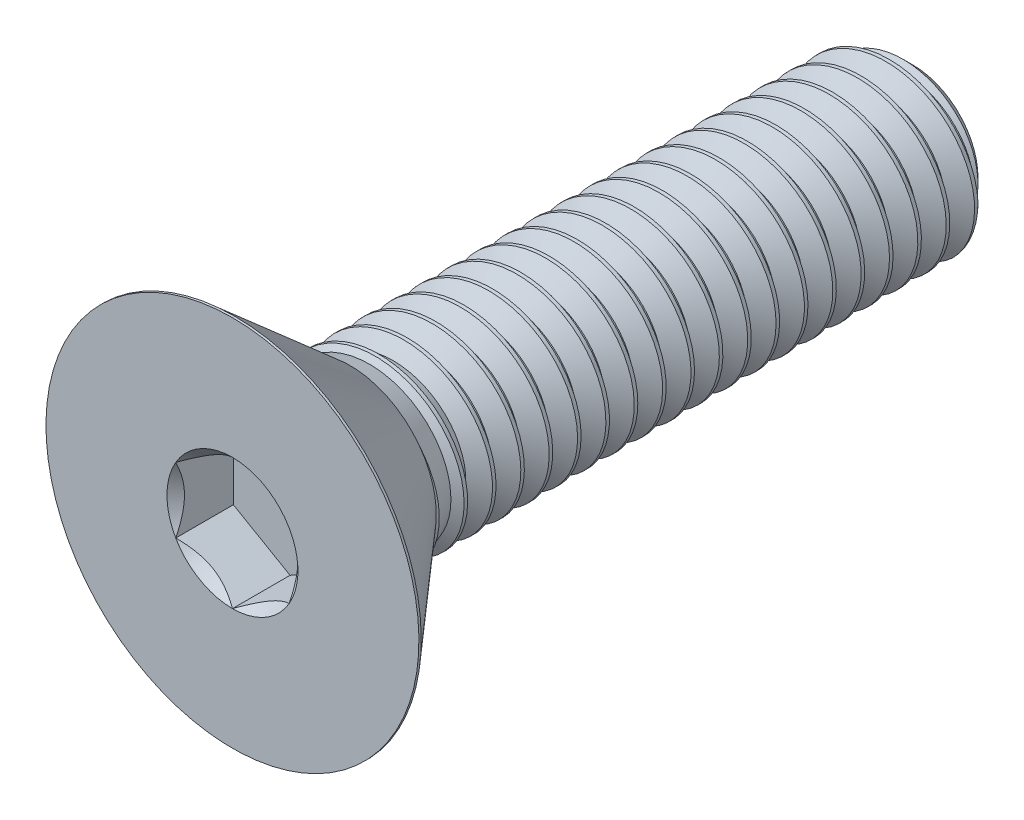
SolidWorks part; units mm, degrees
material "AISI 1020"
ref_plane "Front Plane" through (0, 0, 0) normal (0, 0, 1) x (1, 0, 0)
ref_plane "Top Plane" through (0, 0, 0) normal (0, 1, 0) x (1, 0, 0)
ref_plane "Right Plane" through (0, 0, 0) normal (1, 0, 0) x (0, 0, -1)
sketch "Sketch1" plane through (0, 0, 0) normal (1, 0, 0) x (0, 0, -1)
  line L0 (-9.525, 0) -> (9.525, 0) construction
  line L1 (-9.525, 0) -> (-9.525, 5.2197)
  line L2 (-9.525, 5.2197) -> (-9.4605, 5.2197)
  line L3 (-9.4605, 5.2197) -> (-6.2992, 2.4716)
  line L4 (-9.4605, -5.2197) -> (-6.2992, -2.4716)
  line L5 (9.525, 0) -> (9.525, 2.413)
  line L6 (9.525, 2.413) -> (-6.2992, 2.413)
  line L7 (8.9297, 2.413) -> (9.525, 1.8177)
  line L8 (9.4754, 2.4989) -> (9.8723, 1.8115) construction
  line L9 (9.8723, 1.8115) -> (10.2691, 2.4989) construction
  line L10 (10.2691, 2.4989) -> (9.4754, 2.4989) construction
  line L11 (9.5002, 2.456) -> (10.2443, 2.456)
  line L12 (10.2443, 2.456) -> (9.9219, 1.8974)
  line L13 (9.9219, 1.8974) -> (9.8227, 1.8974)
  line L14 (9.8227, 1.8974) -> (9.5002, 2.456)
  line L15 (9.8723, 1.8974) -> (9.8723, 1.8115) construction
  line L16 (9.525, 2.413) -> (10.2195, 2.413) construction
  line L17 (9.8723, 2.4989) -> (9.8723, 2.413) construction
  line L18 (9.525, -2.413) -> (-6.2992, -2.413)
  arc A0 (-6.2992, 2.4716) -> (-6.1424, 2.413) centre (-6.1424, 2.6521) ccw
  point P2 (0, 0)
  point P23 (-7.9121, 0)
  point P27 (9.8723, 2.456)
  point P30 (8.3344, -2.413)
  point P31 (-6.2992, 5.2197)
  point P33 (-6.2992, -5.2197)
  point P34 (-9.4605, -5.2197)
  dimension "Length" = 19.05
  dimension "Head Height" = 3.2258
  dimension "Head Diameter" = 10.4394
  dimension "Countersink Angle" = 82
  dimension "Screw Size Decimal Equivalent" = 4.826
  dimension "Pitch" = 0.7937
  dimension "D4" = 0.0992
  dimension "D3" = 45
  dimension "D5" = 0.5953
  dimension "D6" = 1.6129
  dimension "D1" = 1.1906
  dimension "D7" = 0.0645
sketch "Sketch8" plane through (0, 0, 0) normal (0, 0, 1) x (1, 0, 0)
  line L1 (0, 1.8331) -> (-1.5875, 0.9165)
  line L2 (-1.5875, 0.9165) -> (-1.5875, -0.9165)
  line L3 (-1.5875, -0.9165) -> (0, -1.8331)
  line L4 (0, -1.8331) -> (1.5875, -0.9165)
  line L5 (1.5875, -0.9165) -> (1.5875, 0.9165)
  line L6 (1.5875, 0.9165) -> (0, 1.8331)
  circle A0 centre (0, 0) radius 1.5875 construction
  dimension "Drive Size" = 3.175
sketch "Sketch2" plane through (0, 0, 0) normal (1, 0, 0) x (0, 0, -1)
  line L0 (-9.4605, 5.2197) -> (-6.2992, 2.4716) construction
  line L1 (-9.525, 0) -> (-9.525, 5.2197) construction
  line L2 (-9.4605, 5.2197) -> (-6.2317, 2.413)
  line L3 (-9.525, 0) -> (-9.525, 5.2197)
  line L4 (-9.525, 5.2197) -> (-9.4605, 5.2197) construction
  line L5 (-9.525, 5.2197) -> (-9.4605, 5.2197)
  line L6 (-6.2317, 2.413) -> (8.9297, 2.413)
  line L7 (8.9297, 2.413) -> (9.525, 1.8177)
  line L8 (9.525, 1.8177) -> (9.525, 0)
  line L9 (9.525, 0) -> (-9.525, 0)
revolve "Revolve1" add sketch "Sketch2" angle 360 about L9
sketch "Sketch9" plane through (0, 0, 9.525) normal (0, 0, 1) x (1, 0, 0)
  line L0 (1.5875, -0.9165) -> (1.5875, 0.9165) construction
  line L1 (0, -1.8331) -> (1.5875, -0.9165) construction
  line L2 (-1.5875, -0.9165) -> (0, -1.8331) construction
  line L3 (-1.5875, 0.9165) -> (-1.5875, -0.9165) construction
  line L4 (0, 1.8331) -> (-1.5875, 0.9165) construction
  line L5 (1.5875, 0.9165) -> (0, 1.8331) construction
  line L6 (1.5875, -0.9165) -> (1.5875, 0.9165)
  line L7 (0, -1.8331) -> (1.5875, -0.9165)
  line L8 (-1.5875, -0.9165) -> (0, -1.8331)
  line L9 (-1.5875, 0.9165) -> (-1.5875, -0.9165)
  line L10 (0, 1.8331) -> (-1.5875, 0.9165)
  line L11 (1.5875, 0.9165) -> (0, 1.8331)
sketch "Sketch10" plane through (0, 0, 9.525) normal (0, 0, 1) x (1, 0, 0)
  circle A0 centre (0, 0) radius 1.8331
extrude "Cut-Extrude2" cut sketch "Sketch10" against normal up to vertex (1.6129 mm away) draft 45 up to point (0, 0, 7.9121)
extrude "Cut-Extrude1" cut sketch "Sketch9" against normal up to vertex (1.6129 mm away) up to point (0, 0, 7.9121)
ref_plane "Plane1" through (0, 0, 6.2317) normal (0, 0, 1) x (1, 0, 0)
split "Split1" trim tools "Plane1" bodies to split 111 resulting bodies 105 106
sketch "Sketch3" plane through (0, 0, -9.525) normal (0, 0, -1) x (-1, 0, 0)
  circle A0 centre (0, 0) radius 2.413 construction
  circle A1 centre (0, 0) radius 2.413
curve "Helix/Spiral1" pitch 0.7937 height 19.05 turns 24
sketch "Sketch4" plane through (0, 0, 0) normal (1, 0, 0) x (0, 0, -1)
  line L0 (9.5002, 2.456) -> (10.2443, 2.456) construction
  line L1 (9.8227, 1.8974) -> (9.5002, 2.456) construction
  line L2 (9.9219, 1.8974) -> (9.8227, 1.8974) construction
  line L3 (10.2443, 2.456) -> (9.9219, 1.8974) construction
  line L4 (9.5002, 2.456) -> (10.2443, 2.456)
  line L5 (9.8227, 1.8974) -> (9.5002, 2.456)
  line L6 (9.9219, 1.8974) -> (9.8227, 1.8974)
  line L7 (10.2443, 2.456) -> (9.9219, 1.8974)
sweep "Cut-Sweep1" cut profiles "Sketch4" path "Helix/Spiral1" align with end faces yes
sketch "Sketch7" plane through (0, 0, 6.2317) normal (0, 0, 1) x (1, 0, 0)
  circle A0 centre (0, 0) radius 2.413
extrude "Boss-Extrude2" add sketch "Sketch7" against normal up to next (15.7567 mm away) draft 20
equation "\"D4@Sketch1\" = \"Pitch@Sketch1\" / 8"
equation "\"D5@Sketch1\"=\"Pitch@Sketch1\"*0.75"
equation "\"D4@Helix/Spiral1\"=\"Pitch@Sketch1\""
equation "\"D3@Helix/Spiral1\"=\"Length@Sketch1\""
equation "\"D6@Sketch1\"=\"Head Height@Sketch1\"/2"
equation "\"D1@Sketch1\"=\"Pitch@Sketch1\"*1.5"
equation "\"D7@Sketch1\"=\"Head Height@Sketch1\"*0.02"
